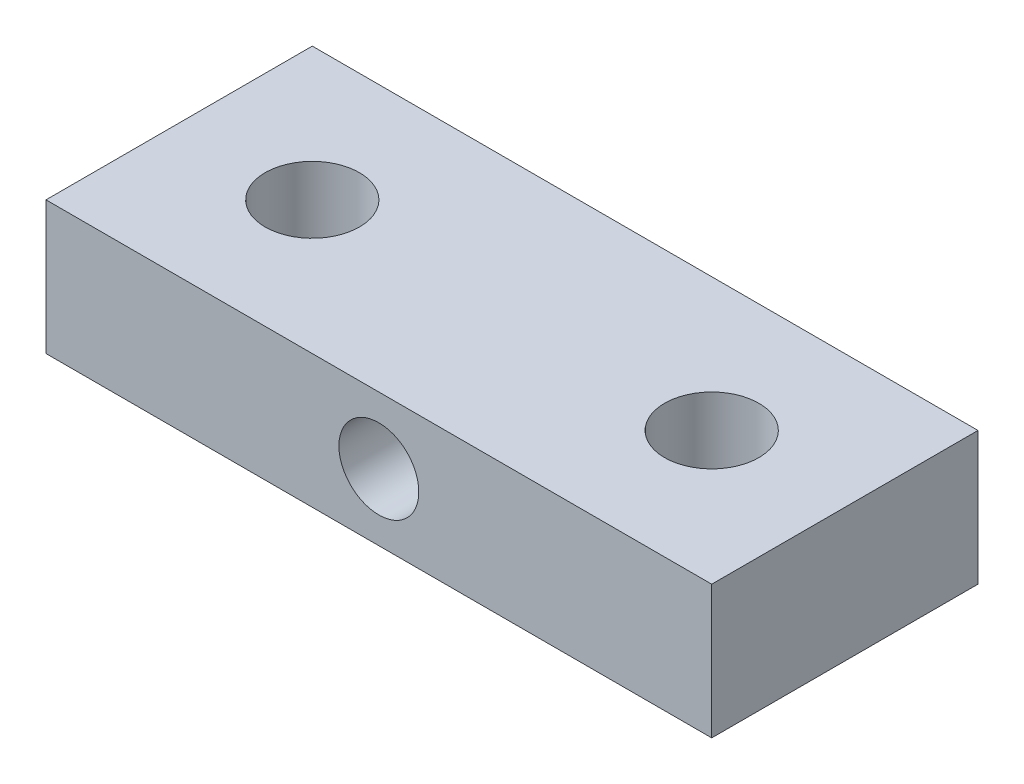
SolidWorks part; units mm, degrees
ref_plane "Front Plane" through (0, 0, 0) normal (0, 0, 1) x (1, 0, 0)
ref_plane "Top Plane" through (0, 0, 0) normal (0, 1, 0) x (1, 0, 0)
ref_plane "Right Plane" through (0, 0, 0) normal (1, 0, 0) x (0, 0, -1)
sketch "Sketch1" plane through (0, 0, 0) normal (0, 1, 0) x (1, 0, 0)
  line L1 (-15.875, -6.35) -> (15.875, -6.35)
  line L2 (-15.875, -6.35) -> (-15.875, 6.35)
  line L3 (-15.875, 6.35) -> (15.875, 6.35)
  line L4 (15.875, -6.35) -> (15.875, 6.35)
  line L5 (-15.875, -6.35) -> (15.875, 6.35) construction
  line L6 (-15.875, 6.35) -> (15.875, -6.35) construction
  point P0 (0, 0)
  dimension "D1" = 31.75
  dimension "D2" = 12.7
extrude "Boss-Extrude1" add sketch "Sketch1" along normal blind 6.35
sketch "Sketch2" plane through (0, 0, -6.35) normal (0, 0, -1) x (-1, 0, 0)
  line L0 (-15.875, 6.35) -> (-15.875, 0) construction
  circle A0 centre (0, 3.175) radius 1.905
  point P3 (-15.875, 3.175)
  dimension "D1" = 3.81
extrude "Cut-Extrude1" cut sketch "Sketch2" against normal through all contours A0
hole_wizard "#8 Clearance Hole1" positions "Sketch3" profile "Sketch4" hole size "#8" standard "ANSI Inch" end condition through all
sketch "Sketch3" plane through (0, 6.35, 0) normal (0, 1, 0) x (1, 0, 0)
  line L0 (-9.525, 0) -> (9.525, 0) construction
  point P1 (-9.525, 0)
  point P2 (9.525, 0)
  point P6 (0, 0)
  point P8 (-9.525, 0)
  point P12 (9.525, 0)
  dimension "D1" = 19.05
sketch "Sketch4" plane through (9.525, 6.35, 0) normal (1, 0, 0) x (0, 0, 1)
  line L0 (0, 0) -> (0, 6.35)
  line L1 (0, 6.35) -> (2.2479, 6.35)
  line L2 (2.2479, 6.35) -> (2.2479, 0)
  line L5 (2.2479, 0) -> (0, 0)
  line L11 (0, -6.35) -> (0, 107.95) construction
  dimension "Thru Hole Dia." = 4.4958
  dimension "Thru Hole Depth" = 6.35
